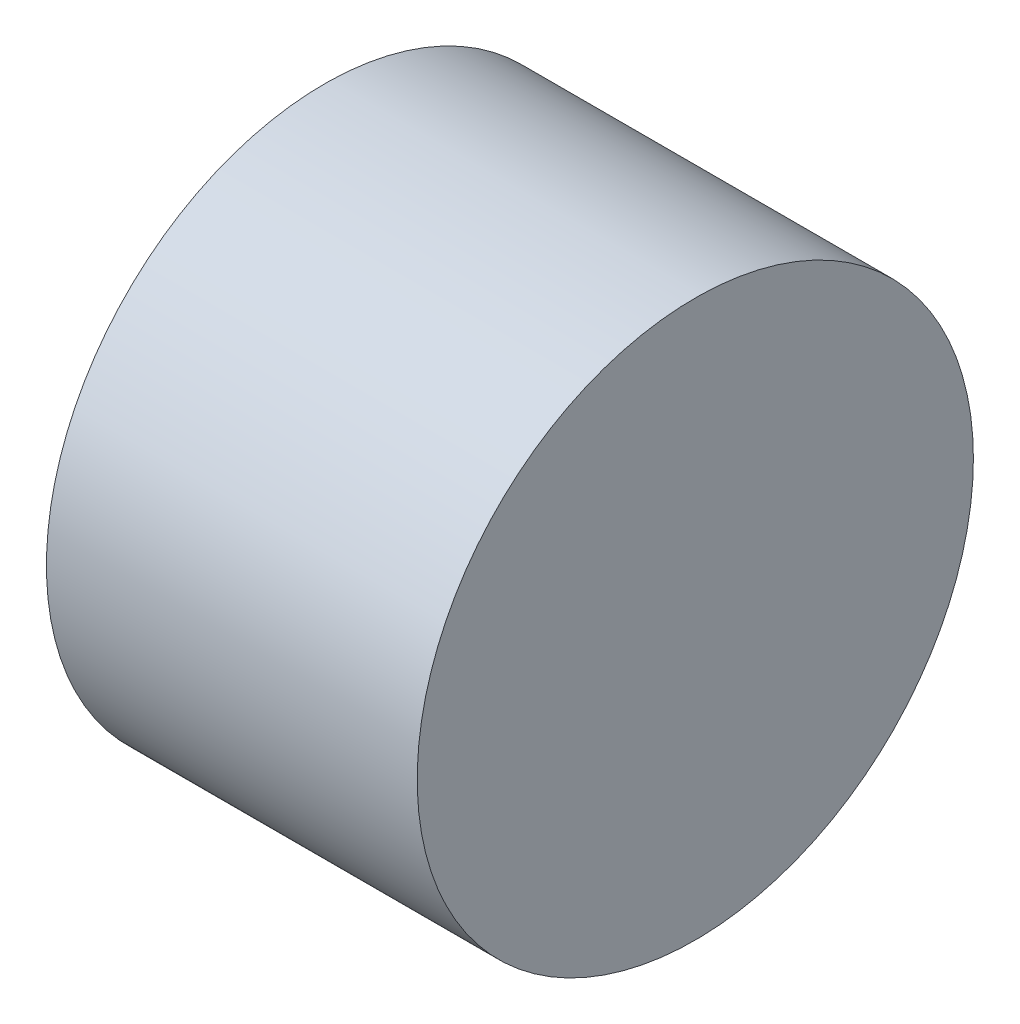
SolidWorks part; units mm, degrees
ref_plane "Front Plane" through (0, 0, 0) normal (0, 0, 1) x (1, 0, 0)
ref_plane "Top Plane" through (0, 0, 0) normal (0, 1, 0) x (1, 0, 0)
ref_plane "Right Plane" through (0, 0, 0) normal (1, 0, 0) x (0, 0, -1)
sketch "Sketch1" plane through (0, 0, 0) normal (1, 0, 0) x (0, 0, -1)
  circle A0 centre (0, 0) radius 75
extrude "Boss-Extrude1" add sketch "Sketch1" along normal blind 50 and the other way blind 50
